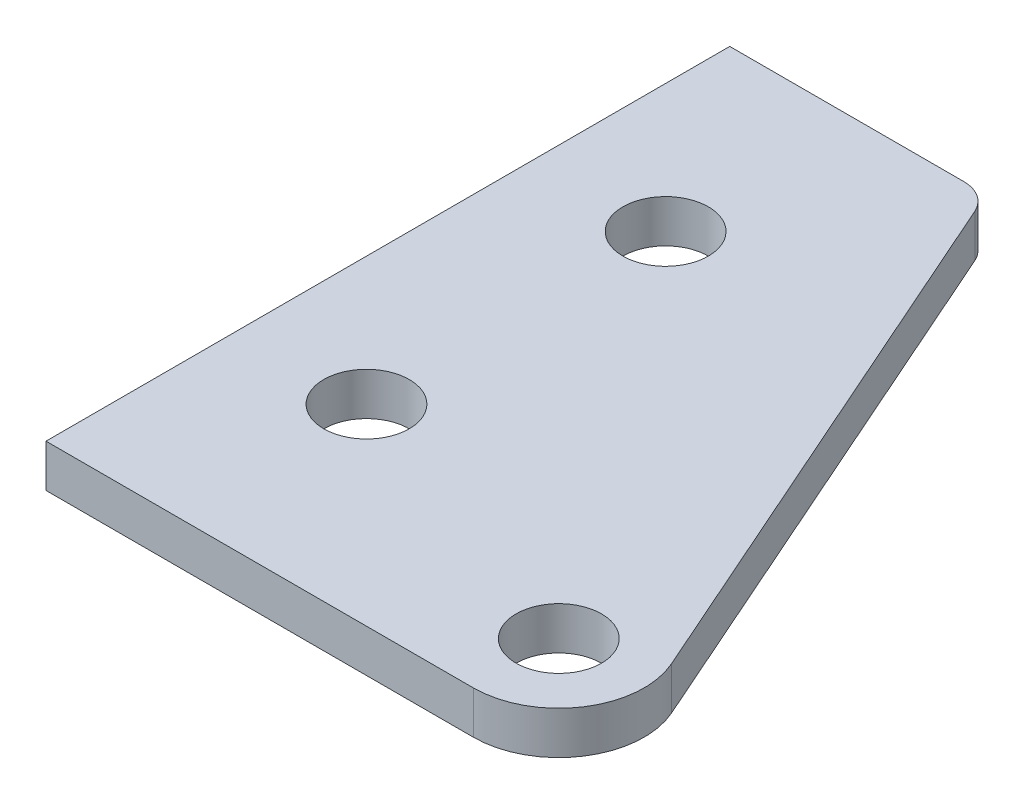
SolidWorks part; units mm, degrees
material "6061-T6 (SS)"
ref_plane "Front" through (0, 0, 0) normal (0, 0, 1) x (1, 0, 0)
ref_plane "Top" through (0, 0, 0) normal (0, 1, 0) x (1, 0, 0)
ref_plane "Right" through (0, 0, 0) normal (1, 0, 0) x (0, 0, -1)
sketch "Sketch1" plane through (0, 0, 0) normal (0, 1, 0) x (1, 0, 0)
  line L0 (0, 0) -> (0, 50.8)
  line L1 (0, 50.8) -> (19.05, 50.8)
  line L2 (0, 0) -> (31.75, 0)
  line L3 (19.05, 50.8) -> (37.5582, 8.9166)
  arc A0 (37.5582, 8.9166) -> (31.75, 0) centre (31.75, 6.35) cw
  dimension "D1" = 50.8
  dimension "D2" = 31.75
  dimension "D3" = 6.35
  dimension "D4" = 19.05
extrude "Boss-Extrude1" add sketch "Sketch1" along normal blind 3.175
hole_wizard "1/4 (0.25) Diameter Hole2" positions "Sketch4" profile "Sketch3" hole size "1/4" standard "ANSI Inch" end condition through all
sketch "Sketch4" plane through (0, 0, 0) normal (0, -1, 0) x (-1, 0, 0)
  point P0 (-31.75, 6.35)
sketch "Sketch3" plane through (31.75, 0, -6.35) normal (1, 0, 0) x (0, 0, -1)
  line L0 (0, 0) -> (0, 3.175)
  line L1 (0, 3.175) -> (3.175, 3.175)
  line L2 (3.175, 3.175) -> (3.175, 0)
  line L5 (3.175, 0) -> (0, 0)
  line L11 (0, -6.35) -> (0, 107.95) construction
  dimension "Thru Hole Dia." = 6.35
  dimension "Thru Hole Depth" = 3.175
hole_wizard "1/4 (0.25) Diameter Hole1" positions "Sketch7" profile "Sketch8" hole size "1/4" standard "ANSI Inch" end condition through all
sketch "Sketch7" plane through (0, 3.175, 0) normal (0, 1, 0) x (1, 0, 0)
  line L4 (0, 0) -> (31.75, 0) construction
  line L7 (9.525, 50.8) -> (9.525, 0)
  line L8 (19.05, 50.8) -> (0, 50.8) construction
  point P0 (9.525, 36.5125)
  point P2 (9.525, 14.2875)
  dimension "D1" = 22.225
  dimension "D2" = 14.2875
sketch "Sketch8" plane through (9.525, 3.175, -36.5125) normal (1, 0, 0) x (0, 0, 1)
  line L0 (0, 0) -> (0, 3.175)
  line L1 (0, 3.175) -> (3.175, 3.175)
  line L2 (3.175, 3.175) -> (3.175, 0)
  line L5 (3.175, 0) -> (0, 0)
  line L11 (0, -6.35) -> (0, 107.95) construction
  dimension "Thru Hole Dia." = 6.35
  dimension "Thru Hole Depth" = 3.175
fillet "Fillet1" radius 2.54 1 edges at (19.05, 1.5875, -50.8)
